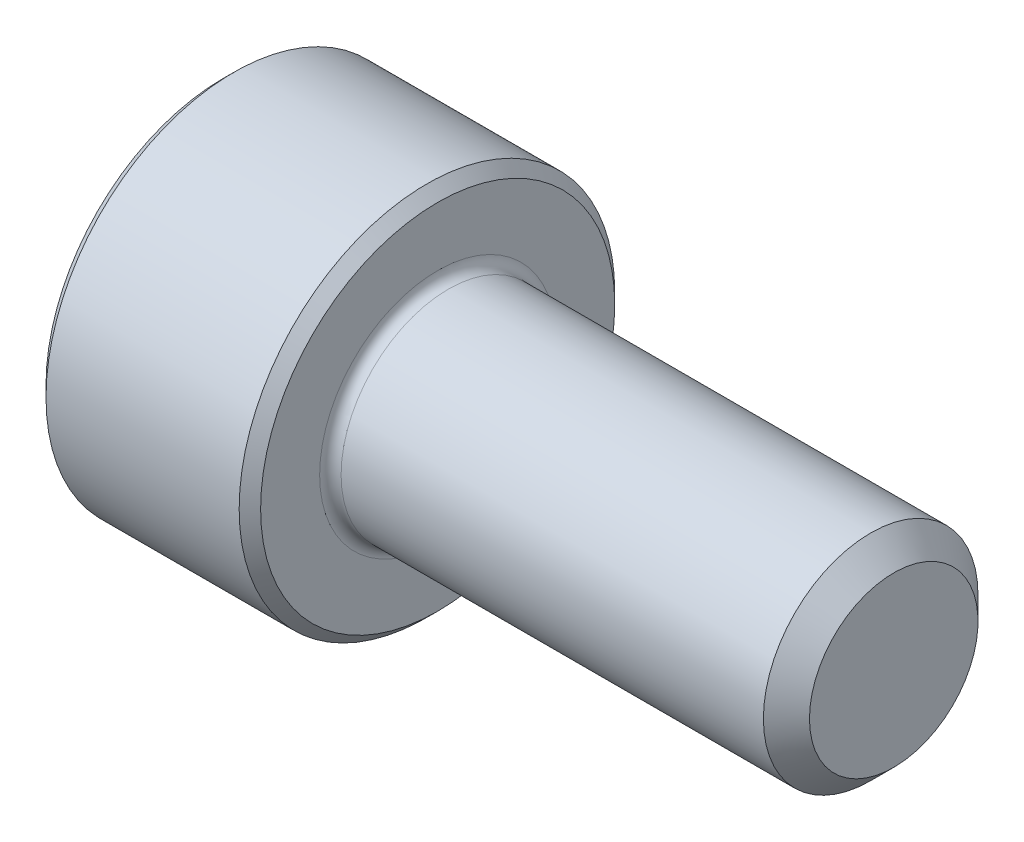
SolidWorks part; units mm, degrees
ref_plane "前视基准面" through (0, 0, 0) normal (0, 0, 1) x (1, 0, 0)
ref_plane "上视基准面" through (0, 0, 0) normal (0, 1, 0) x (1, 0, 0)
ref_plane "右视基准面" through (0, 0, 0) normal (1, 0, 0) x (0, 0, -1)
sketch "草图1" plane through (0, 0, 0) normal (0, 0, 1) x (1, 0, 0)
  line L0 (0, 0) -> (0, 3.3)
  line L1 (0, 3.3) -> (0.2, 3.5)
  line L2 (0.2, 3.5) -> (3.8, 3.5)
  line L3 (3.8, 3.5) -> (4, 3.3)
  line L4 (4, 3.3) -> (4, 2.2)
  line L5 (4.2, 2) -> (12.0705, 2)
  line L6 (12.0705, 2) -> (12.5, 1.5705)
  line L7 (12.5, 1.5705) -> (12.5, 0)
  line L8 (12.5, 0) -> (0, 0)
  line L9 (12.5, 0) -> (0, 0) construction
  arc A0 (4, 2.2) -> (4.2, 2) centre (4.2, 2.2) ccw
revolve "旋转1" add sketch "草图1" angle 360 about L9 reverse direction yes
cosmetic thread "装饰螺纹线1" parameters "D1"=7.5, "D2"=3.141
sketch "草图2" plane through (0, 0, 0) normal (1, 0, 0) x (0, 0, -1)
  line L0 (-1.5, 0.866) -> (-1.5, -0.866)
  line L1 (-1.5, -0.866) -> (0, -1.7321)
  line L2 (0, -1.7321) -> (1.5, -0.866)
  line L3 (1.5, -0.866) -> (1.5, 0.866)
  line L4 (1.5, 0.866) -> (0, 1.7321)
  line L5 (0, 1.7321) -> (-1.5, 0.866)
extrude "切除-拉伸1" cut sketch "草图2" along normal blind 2
ref_plane "基准面1" through (4, 0, 0) normal (1, 0, 0) x (0, 0, -1)
ref_plane "for_plate XY" through (4, 0, 0) normal (1, 0, 0) x (0, 0, -1)
ref_plane "for_plate XZ" through (0, 0, 0) normal (0, -1, 0) x (-1, 0, 0)
ref_plane "for_plate YZ" through (0, 0, 0) normal (0, 0, -1) x (-1, 0, 0)
ref_axis "for_plate X" through (4, 0, 80.9) along (0, 0, -1)
ref_axis "for_plate Y" through (4, -50, 0) along (0, 1, 0)
ref_axis "for_plate Z" through (80.9, 0, 0) along (-1, 0, 0)
sketch3d "for_plate"
  point P0 (4, 0, 0)
